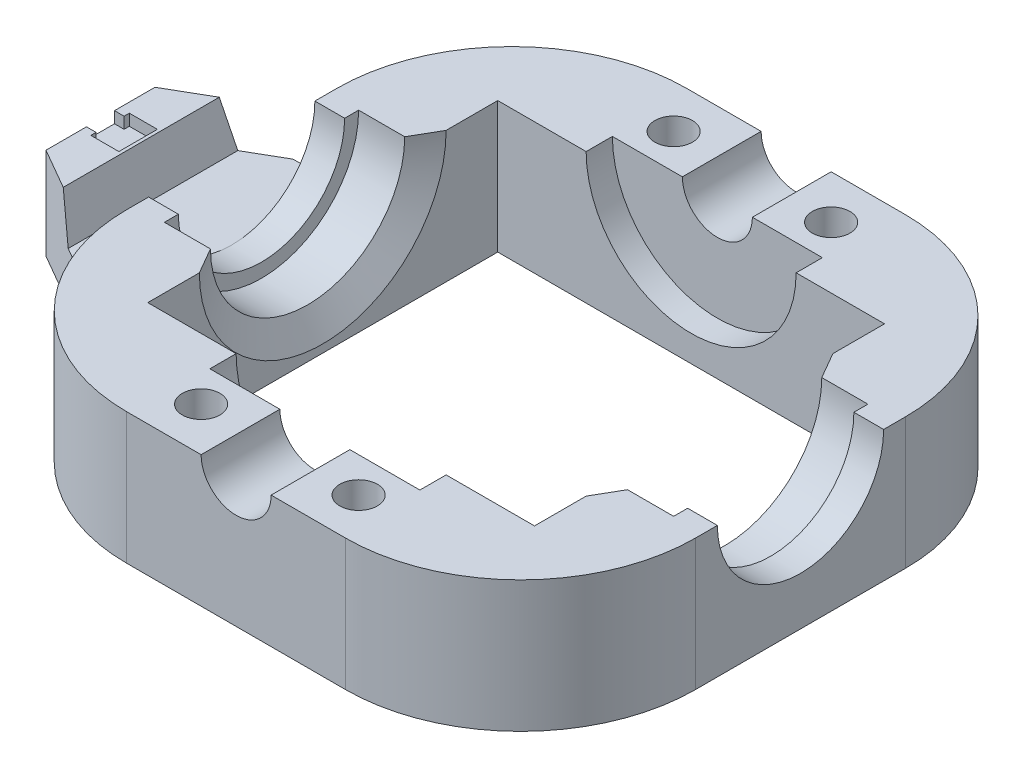
SolidWorks part; units mm, degrees
ref_plane "Спереди" through (0, 0, 0) normal (0, 0, 1) x (1, 0, 0)
ref_plane "Сверху" through (0, 0, 0) normal (0, 1, 0) x (1, 0, 0)
ref_plane "Справа" through (0, 0, 0) normal (1, 0, 0) x (0, 0, -1)
sketch "Sketch1" plane through (0, 0, 0) normal (0, 1, 0) x (1, 0, 0)
  line L1 (32.5, -32) -> (-32.5, -32)
  line L2 (32.5, -32) -> (32.5, 32)
  line L3 (32.5, 32) -> (-32.5, 32)
  line L4 (-32.5, -32) -> (-32.5, 32)
  line L5 (32.5, -32) -> (-32.5, 32) construction
  line L6 (32.5, 32) -> (-32.5, -32) construction
  line L7 (22.1, -20) -> (-22.1, -20)
  line L8 (22.1, -20) -> (22.1, 20)
  line L9 (22.1, 20) -> (-22.1, 20)
  line L10 (-22.1, -20) -> (-22.1, 20)
  line L11 (22.1, -20) -> (-22.1, 20) construction
  line L12 (22.1, 20) -> (-22.1, -20) construction
  point P0 (0, 0)
  point P6 (0, 0)
  dimension "D1" = 65
  dimension "D2" = 64
  dimension "D3" = 40
  dimension "D4" = 44.2
extrude "Boss-Extrude1" add sketch "Sketch1" along normal blind 15
sketch "Sketch3" plane through (0, 15, 0) normal (0, 1, 0) x (1, 0, 0)
  line L0 (-22.1, 0) -> (-32.5, 0) construction
  line L1 (-22.1, 20) -> (-22.1, -20) construction
  line L2 (-32.5, 32) -> (-32.5, -32) construction
  line L3 (22.1, 0) -> (32.5, 0) construction
  line L4 (22.1, -20) -> (22.1, 20) construction
  line L5 (32.5, -32) -> (32.5, 32) construction
  line L10 (22.1, -11.1) -> (29.1, -11.1)
  line L11 (22.1, -11.1) -> (22.1, 0)
  line L12 (22.1, 0) -> (29.1, 0)
  line L13 (29.1, -11.1) -> (29.1, 0)
  line L14 (22.1, -11.1) -> (29.1, 0) construction
  line L15 (22.1, 0) -> (29.1, -11.1) construction
  line L16 (-29.1, -11.1) -> (-22.1, -11.1)
  line L17 (-29.1, -11.1) -> (-29.1, 0)
  line L18 (-29.1, 0) -> (-22.1, 0)
  line L19 (-22.1, -11.1) -> (-22.1, 0)
  line L20 (-29.1, -11.1) -> (-22.1, 0) construction
  line L21 (-29.1, 0) -> (-22.1, -11.1) construction
  point P18 (25.6, -5.55)
  point P23 (-25.6, -5.55)
  dimension "D1" = 7
  dimension "D2" = 11.1
revolve "Cut-Revolve1" cut sketch "Sketch3" angle 360 about L12
sketch "Sketch4" plane through (32.5, 0, 0) normal (1, 0, 0) x (0, 0, -1)
  line L0 (-32, 15) -> (32, 15) construction
  circle A0 centre (0, 15) radius 9.5
  dimension "D1" = 19
extrude "Cut-Extrude2" cut sketch "Sketch4" against normal through all
sketch "Sketch5" plane through (0, 0, 32) normal (0, 0, 1) x (1, 0, 0)
  line L0 (-32.5, 15) -> (32.5, 15) construction
  circle A0 centre (0, 15) radius 4
  dimension "D1" = 8
extrude "Cut-Extrude3" cut sketch "Sketch5" against normal through all
sketch "Sketch8" plane through (0, 15, 0) normal (0, 1, 0) x (1, 0, 0)
  line L1 (-18, -16.5) -> (18, -16.5) construction
  line L2 (-18, -16.5) -> (-18, 16.5) construction
  line L3 (-18, 16.5) -> (18, 16.5) construction
  line L4 (18, -16.5) -> (18, 16.5) construction
  line L5 (-18, -16.5) -> (18, 16.5) construction
  line L6 (-18, 16.5) -> (18, -16.5) construction
  line L7 (-9, 27) -> (9, 27) construction
  line L8 (-9, 27) -> (-9, -27) construction
  line L9 (-9, -27) -> (9, -27) construction
  line L10 (9, 27) -> (9, -27) construction
  line L11 (-9, 27) -> (9, -27) construction
  line L12 (-9, -27) -> (9, 27) construction
  circle A0 centre (18, 16.5) radius 2.15
  circle A1 centre (18, -16.5) radius 2.15
  circle A2 centre (-18, -16.5) radius 2.15
  circle A3 centre (-18, 16.5) radius 2.15
  circle A4 centre (9, -27) radius 2.15
  circle A5 centre (-9, -27) radius 2.15
  circle A6 centre (-9, 27) radius 2.15
  circle A7 centre (9, 27) radius 2.15
  point P0 (0, 0)
  point P10 (0, 0)
  dimension "D3" = 4.3
  dimension "D1" = 33
  dimension "D2" = 36
  dimension "D4" = 18
  dimension "D5" = 54
extrude "Cut-Extrude6" cut sketch "Sketch8" against normal through all
fillet "Fillet1" radius 20 4 edges at (-32.5, 7.5, 32) (-32.5, 7.5, -32) (32.5, 7.5, -32) (32.5, 7.5, 32)
chamfer "Chamfer1" distance 3 angle 30 2 edges at (-22.1, 3.9, 0) (22.1, 3.9, 0) first distance on face at (-22.1, 8.15, 0) first distance on face at (22.1, 8.15, 0)
sketch "Sketch9" plane through (0, 15, 0) normal (0, 1, 0) x (1, 0, 0)
  line L0 (0, 29.8714) -> (0, -31.0419) construction
  line L1 (-4, 20) -> (-22.1, 20) construction
  line L2 (-12, -23) -> (0, -23)
  line L3 (-12, -23) -> (-12, -20)
  line L4 (-12, -20) -> (0, -20)
  line L5 (0, -23) -> (0, -20)
  line L6 (-12, -23) -> (0, -20) construction
  line L7 (-12, -20) -> (0, -23) construction
  line L8 (-12, 20) -> (0, 20)
  line L9 (-12, 20) -> (-12, 23)
  line L10 (-12, 23) -> (0, 23)
  line L11 (0, 20) -> (0, 23)
  line L12 (-12, 20) -> (0, 23) construction
  line L13 (-12, 23) -> (0, 20) construction
  line L14 (-22.1, -20) -> (-4, -20) construction
  point P3 (-6, -21.5)
  point P8 (-6, 21.5)
  dimension "D1" = 3
  dimension "D2" = 12
revolve "Cut-Revolve2" cut sketch "Sketch9" angle 360 about L0
sketch "Sketch10" plane through (-32.5, 0, 0) normal (-1, 0, 0) x (0, 0, 1)
  line L0 (-9.5, 15) -> (9.5, 15) construction
  line L1 (0, 15) -> (0, 0) construction
  line L2 (-12, 0) -> (12, 0) construction
  line L4 (12, 5.5) -> (-12, 5.5)
  line L5 (12, 5.5) -> (12, 0)
  line L6 (12, 0) -> (-12, 0)
  line L7 (-12, 5.5) -> (-12, 0)
  line L8 (12, 5.5) -> (-12, 0) construction
  line L9 (12, 0) -> (-12, 5.5) construction
  arc A0 (-9.5, 15) -> (9.5, 15) centre (0, 15) ccw construction
  point P8 (0, 2.75)
extrude "Boss-Extrude2" add sketch "Sketch10" along normal blind 15
sketch "Sketch12" plane through (-32.5, 0, 0) normal (-1, 0, 0) x (0, 0, 1)
  line L0 (-9.5, 15) -> (9.5, 15) construction
  line L1 (0, 15) -> (0, 0) construction
  line L3 (12, 9.2) -> (-12, 9.2)
  line L4 (12, 9.2) -> (12, 5.5)
  line L5 (12, 5.5) -> (-12, 5.5)
  line L6 (-12, 9.2) -> (-12, 5.5)
  line L7 (12, 9.2) -> (-12, 5.5) construction
  line L8 (12, 5.5) -> (-12, 9.2) construction
  point P7 (0, 7.35)
  dimension "D1" = 5.8
extrude "Boss-Extrude3" add sketch "Sketch12" along normal up to surface (15 mm away) from offset 9 up to face at (-47.5, 2.75, 0)
sketch "Sketch13" plane through (0, 9.2, 0) normal (0, 1, 0) x (1, 0, 0)
  line L0 (-41.5, 0) -> (-47.5, 0) construction
  line L1 (-41.5, -12) -> (-41.5, 12) construction
  line L2 (-47.5, 12) -> (-47.5, -12) construction
  line L3 (-46.4, 2.2) -> (-46.4, 1.6)
  line L4 (-46.4, -2.2) -> (-43.2, -2.2)
  line L5 (-46.4, 1.6) -> (-47.5, 1.6)
  line L6 (-46.4, 2.2) -> (-43.2, 2.2)
  line L7 (-43.2, -2.2) -> (-43.2, 2.2)
  line L8 (-46.4, -2.2) -> (-43.2, 2.2) construction
  line L9 (-46.4, 2.2) -> (-43.2, -2.2) construction
  line L10 (-46.4, -2.2) -> (-46.4, -1.6)
  line L11 (-46.4, -1.6) -> (-47.5, -1.6)
  line L12 (-47.5, -1.6) -> (-47.5, -12)
  line L13 (-47.5, -12) -> (-41.5, -12)
  line L14 (-41.5, -12) -> (-41.5, 12)
  line L15 (-41.5, 12) -> (-47.5, 12)
  line L16 (-47.5, 12) -> (-47.5, 1.6)
  point P6 (-44.8, 0)
  dimension "D1" = 3.2
  dimension "D2" = 4.4
  dimension "D3" = 3.2
  dimension "D4" = 2.7
extrude "Boss-Extrude4" add sketch "Sketch13" along normal blind 1.3
chamfer "Chamfer2" distance 5 angle 15 1 edges at (-41.5, 10.5, 0) first distance on face at (-41.5, 8, 0)
chamfer "Chamfer3" distance 10 angle 30 2 edges at (-47.5, 5.25, 12) (-47.5, 5.25, -12) first distance on face at (-40.7233, 5.3333, 12) first distance on face at (-40.7233, 5.3333, -12)
